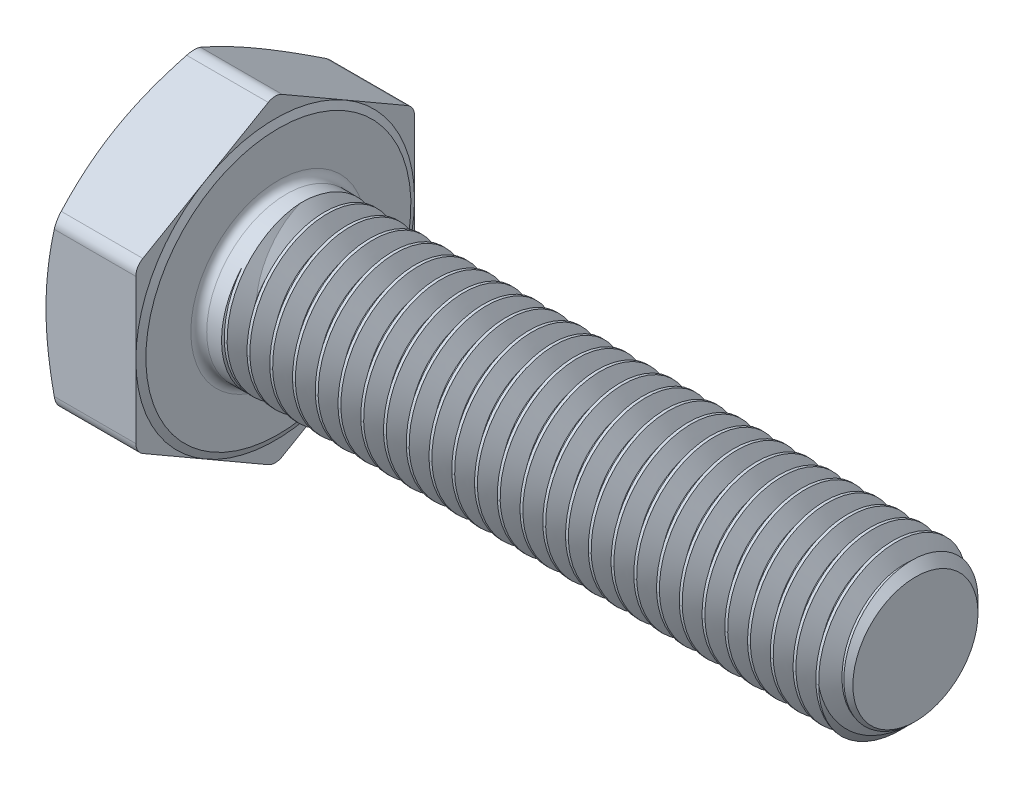
SolidWorks part; units mm, degrees
ref_plane "Front Plane" through (0, 0, 0) normal (0, 0, 1) x (1, 0, 0)
ref_plane "Top Plane" through (0, 0, 0) normal (0, 1, 0) x (1, 0, 0)
ref_plane "Right Plane" through (0, 0, 0) normal (1, 0, 0) x (0, 0, -1)
sketch "Sketch1" plane through (0, 0, 0) normal (0, 0, 1) x (1, 0, 0)
  line L0 (0, 0) -> (25.4, 0) construction
  line L1 (0, 0) -> (-3.9688, 0) construction
  line L2 (0, 5.5562) -> (0, -5.5562) construction
  line L3 (-3.9688, 5.5562) -> (-3.9687, -5.5563) construction
  line L4 (25.4, 3.175) -> (25.4, -3.175) construction
  line L8 (24.4929, 3.175) -> (25.4, 3.175) construction
  point P8 (24.4929, 0)
  point P11 (22.225, -3.175)
  point P12 (0.9071, 0)
  dimension "Head Height" = 3.9688
  dimension "Head Width" = 11.1125
  dimension "Length" = 25.4
  dimension "Thread Size" = 6.35
  dimension "D1" = 3.175
  dimension "Thread Pitch" = 0.9071
  dimension "D2" = 0.9071
sketch "Sketch2" plane through (0, 0, 0) normal (1, 0, 0) x (0, 0, -1)
  circle A0 centre (0, 0) radius 3.175
extrude "Boss-Extrude1" add sketch "Sketch2" along normal up to vertex (25.4 mm away) up to point (25.4, 3.175, 0)
sketch "Sketch3" plane through (0, 0, 0) normal (-1, 0, 0) x (0, 0, 1)
  line L0 (0, 6.4158) -> (0, 0) construction
  line L1 (0, 6.4158) -> (-5.5563, 3.2079)
  line L2 (-5.5563, 3.2079) -> (-5.5563, -3.2079)
  line L3 (-5.5563, -3.2079) -> (0, -6.4158)
  line L4 (0, -6.4158) -> (5.5562, -3.2079)
  line L5 (5.5562, -3.2079) -> (5.5562, 3.2079)
  line L6 (5.5562, 3.2079) -> (0, 6.4158)
  circle A0 centre (0, 0) radius 5.5562 construction
extrude "Boss-Extrude2" add sketch "Sketch3" along normal up to vertex (3.9688 mm away) up to point (-3.9688, 5.5562, 0)
sketch "Sketch5" plane through (-3.9688, 0, 0) normal (-1, 0, 0) x (0, 0, 1)
  circle A0 centre (0, 0) radius 5.5562 construction
  circle A1 centre (0, 0) radius 5.5562 construction
  circle A2 centre (0, 0) radius 5.0006
  dimension "D1" = 0.5556
extrude "Cut-Extrude1" cut sketch "Sketch5" against normal up to vertex (3.9688 mm away) draft 65 flip side to cut up to point (0, 0, 0)
sketch "Sketch11" plane through (-3.9688, 0, 0) normal (-1, 0, 0) x (0, 0, 1)
  line L0 (0, 3.9449) -> (0, 2.4448) construction
  line L1 (0.2223, 3.9449) -> (0.2223, 2.4448)
  line L2 (-0.2222, 3.9449) -> (-0.2222, 2.4448)
  arc A0 (0.2223, 3.9449) -> (-0.2222, 3.9449) centre (0, 3.9449) ccw
  arc A1 (-0.2222, 2.4448) -> (0.2223, 2.4448) centre (0, 2.4448) ccw
  circle A2 centre (0, 0) radius 4.1672 construction
  circle A3 centre (0, 0) radius 2.2225 construction
  point P3 (0, 3.1948)
  dimension "D1" = 8.3344
  dimension "D2" = 4.445
  dimension "D3" = 0.4445
extrude "Boss-Extrude5" add sketch "Sketch11" along normal blind 0.0635
fillet "Fillet5" radius 0.0635 4 edges at (-4.0323, 3.1948, 0.2223) (-4.0323, 2.2225, 0) (-4.0323, 3.1948, -0.2222) (-4.0323, 4.1672, 0)
pattern_circular "CirPattern1" count 6 over 360 about axis through (0, 0, 0) along (-1, 0, 0) of "Boss-Extrude5", "Fillet5" reverse direction yes
fillet "Fillet7" radius 0.5556 6 edges at (-1.6544, -6.4158, 0) (-1.6544, -3.2079, -5.5563) (-1.6544, 3.2079, -5.5563) (-1.6544, 6.4158, 0) (-1.6544, -3.2079, 5.5562) (-1.6544, 3.2079, 5.5562)
chamfer "Chamfer1" distance 0.6804 angle 45 1 edges at (25.4, 0, -3.175)
sketch "Sketch15" plane through (0, 0, 0) normal (0, 0, 1) x (1, 0, 0)
  line L0 (0, 5.2839) -> (-0.127, 5.5562)
  line L1 (0, 5.5562) -> (0, -5.5562) construction
  line L2 (-0.127, 5.5562) -> (-0.127, 6.4158)
  line L3 (-0.127, 6.4158) -> (0, 6.4158)
  line L4 (0, 6.4158) -> (0, 5.2839)
  dimension "D1" = 0.127
  dimension "D2" = 25
revolve "Cut-Revolve1" cut sketch "Sketch15" angle 360 about L1
fillet "Fillet4" radius 0.3175 1 edges at (0, 0, 3.175)
sketch "Reference Sketch1" plane through (0, 0, 0) normal (1, 0, 0) x (0, 0, -1)
  line L1 (0, 6.4158) -> (-5.5563, 3.2079)
  line L2 (-5.5563, 3.2079) -> (-5.5563, -3.2079)
  line L3 (-5.5563, -3.2079) -> (0, -6.4158)
  line L4 (0, -6.4158) -> (5.5563, -3.2079)
  line L5 (5.5563, -3.2079) -> (5.5563, 3.2079)
  line L6 (5.5563, 3.2079) -> (0, 6.4158)
  circle A0 centre (0, 0) radius 5.5563 construction
  circle A1 centre (0, 0) radius 5.5562
sketch "Sketch12" plane through (25.4, 0, 0) normal (1, 0, 0) x (0, 0, -1)
  circle A1 centre (0, 0) radius 3.175
ref_plane "Plane2" through (0.9071, 0, 0) normal (1, 0, 0) x (0, 0, -1)
split "Split1" trim tools "Plane2" bodies to split 126 116 resulting bodies 118 119
curve "Helix/Spiral2" pitch 0.9071 height 26.3071 radius 3.175 centre (25.4, 0, 0) axis (-1, 0, 0) start towards (0, 1, 0) parameters "Pitch"=0.9071
sketch "Sketch13" plane through (0, 0, 0) normal (0, 0, 1) x (1, 0, 0)
  line L0 (25.3433, 3.2732) -> (25.7969, 2.4876) construction
  line L1 (25.7969, 2.4876) -> (26.2504, 3.2732) construction
  line L2 (26.2504, 3.2732) -> (25.3433, 3.2732) construction
  line L3 (25.7969, 2.4876) -> (25.7969, 2.5858) construction
  line L4 (25.4, 3.175) -> (26.1937, 3.175)
  line L5 (25.7969, 3.175) -> (25.7969, 3.2732) construction
  line L6 (26.1937, 3.175) -> (25.8536, 2.5858)
  line L7 (25.8536, 2.5858) -> (25.7402, 2.5858)
  line L8 (25.7402, 2.5858) -> (25.4, 3.175)
  line L9 (24.4929, 3.175) -> (25.4, 3.175) construction
  dimension "D1" = 0.1134
sweep "Cut-Sweep1" cut profiles "Sketch13" path "Helix/Spiral2" align with end faces yes
sketch "Sketch14" plane through (0.9071, 0, 0) normal (1, 0, 0) x (0, 0, -1)
  circle A1 centre (0, 0) radius 3.175
  circle A2 centre (0, 0) radius 3.175
  dimension "D1" = 0
extrude "Boss-Extrude4" add sketch "Sketch14" along normal through all draft 50
equation "\"D1@Sketch11\"=\"Head Width@Sketch1\" * 0.75"
equation "\"D2@Sketch11\"=\"Head Width@Sketch1\"*0.4"
equation "\"D3@Sketch11\"=\"Head Width@Sketch1\" * .04"
equation "\"D3@Helix/Spiral2\"=\"Length@Sketch1\" + \"Thread Pitch@Sketch1\""
equation "\"D1@Chamfer1\"=\"Thread Pitch@Sketch1\"*0.750"
equation "\"D1@Sketch1\"=\"Thread Pitch@Sketch1\"*3.5"
equation "\"Pitch@Helix/Spiral2\"=\"Thread Pitch@Sketch1\""
equation "\"D1@Sketch13\"=\"Thread Pitch@Sketch1\"*0.125"
equation "\"D1@Sketch5\"=\"Head Width@Sketch1\"*0.05"
equation "\"D1@Fillet4\"=\"Thread Size@Sketch1\"*0.05"
equation "\"D2@Sketch1\"=\"Thread Pitch@Sketch1\""
equation "\"D1@Fillet7\"=\"Head Width@Sketch1\"*0.05"
